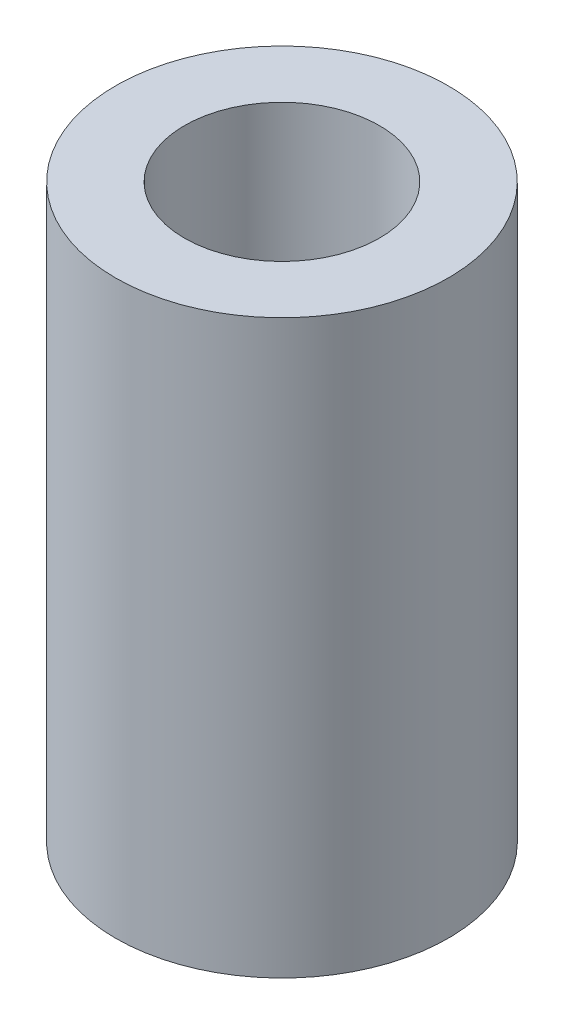
SolidWorks part; units mm, degrees
ref_plane "Front Plane" through (0, 0, 0) normal (0, 0, 1) x (1, 0, 0)
ref_plane "Top Plane" through (0, 0, 0) normal (0, 1, 0) x (1, 0, 0)
ref_plane "Right Plane" through (0, 0, 0) normal (1, 0, 0) x (0, 0, -1)
sketch "Sketch1" plane through (0, 0, 0) normal (0, 1, 0) x (1, 0, 0)
  circle A0 centre (0, 0) radius 10
  dimension "SLEEVE_OD" = 20
extrude "Boss-Extrude1" add sketch "Sketch1" along normal blind 34.3646
sketch "Sketch2" plane through (0, 0, 0) normal (0, 1, 0) x (1, 0, 0)
  circle A0 centre (0, 0) radius 5.8605
  dimension "BORE_D" = 11.7209
extrude "Cut-Extrude1" cut sketch "Sketch2" along normal through all
chamfer "Chamfer1" distance 1.801 angle 60 rebuild error yes
